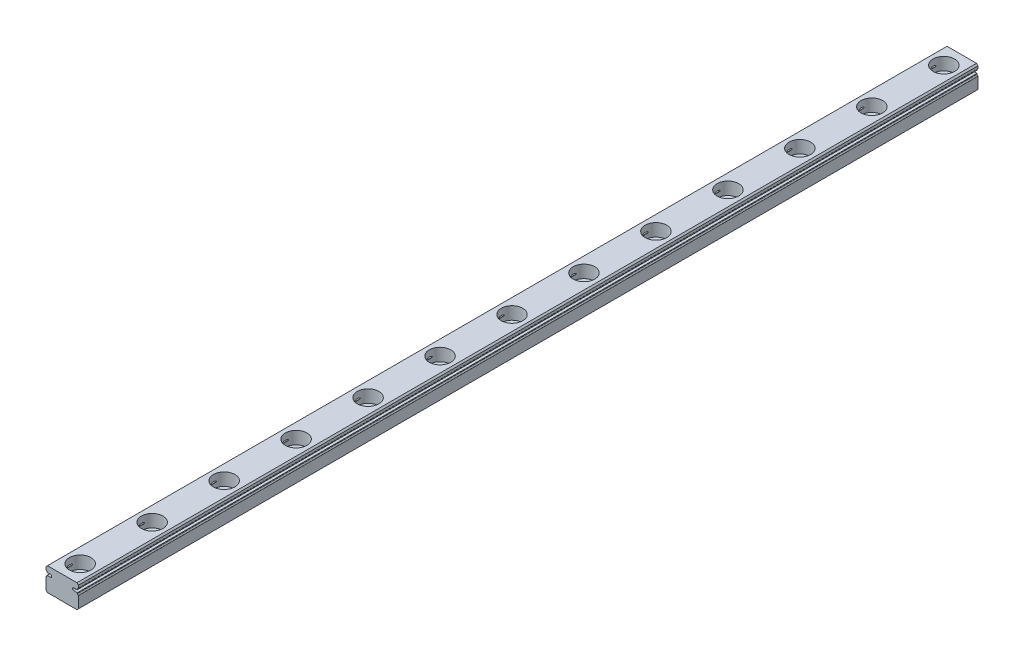
SolidWorks part; units mm, degrees
material "Acero al carbono no aleado"
ref_plane "Alzado" through (0, 0, 0) normal (0, 0, 1) x (1, 0, 0)
ref_plane "Planta" through (0, 0, 0) normal (0, 1, 0) x (1, 0, 0)
ref_plane "Vista lateral" through (0, 0, 0) normal (1, 0, 0) x (0, 0, -1)
ref_plane "Plano1" through (0, 3.3057, 0) normal (0, 1, 0) x (1, 0, 0)
sketch "Croquis1" plane through (0, 3.3057, 0) normal (0, 1, 0) x (1, 0, 0)
  line L0 (4.5, 250) -> (-4.5, 250)
  line L1 (-4.5, 250) -> (-4.5, -250)
  line L2 (-4.5, -250) -> (4.5, -250)
  line L3 (4.5, -250) -> (4.5, 250)
extrude "Saliente-Extruir1" add sketch "Croquis1" against normal blind 6.5
sketch "Croquis2" plane through (0, 0, -250) normal (0, 0, -1) x (-1, 0, 0)
  line L0 (1.6, -3.1943) -> (2.1, -3.1943)
  arc A0 (2.1, -3.1943) -> (1.6, -3.1943) centre (1.85, -3.4568) ccw
extrude "Cortar-Extruir1" cut sketch "Croquis2" against normal through all
sketch "Croquis3" plane through (0, 0, -250) normal (0, 0, -1) x (-1, 0, 0)
  line L0 (-4.5, 1.6457) -> (-4.5, 0.9457)
  line L1 (-4.5, 0.9457) -> (-3.25, 0.9457)
  line L2 (-3.25, 1.6457) -> (-4.5, 1.6457)
  arc A0 (-3.25, 0.9457) -> (-3.25, 1.6457) centre (-3.25, 1.2957) ccw
extrude "Cortar-Extruir2" cut sketch "Croquis3" against normal through all
sketch "Croquis4" plane through (0, 0, -250) normal (0, 0, -1) x (-1, 0, 0)
  line L0 (-4.3353, 0.9457) -> (-4.5, 0.9457)
  line L1 (-4.5, 0.9457) -> (-4.5, 0.4169)
  arc A0 (-4.5, 0.4169) -> (-4.3353, 0.9457) centre (-4.622, 0.745) ccw
extrude "Cortar-Extruir3" cut sketch "Croquis4" against normal through all
sketch "Croquis5" plane through (0, 0, -250) normal (0, 0, -1) x (-1, 0, 0)
  line L0 (-4.5, 2.1744) -> (-4.5, 1.6457)
  line L1 (-4.5, 1.6457) -> (-4.3353, 1.6457)
  arc A0 (-4.3353, 1.6457) -> (-4.5, 2.1744) centre (-4.622, 1.8464) ccw
extrude "Cortar-Extruir4" cut sketch "Croquis5" against normal through all
sketch "Croquis6" plane through (0, 0, -250) normal (0, 0, -1) x (-1, 0, 0)
  line L0 (4.5, 0.9457) -> (4.5, 1.6457)
  line L1 (4.5, 1.6457) -> (3.25, 1.6457)
  line L2 (3.25, 0.9457) -> (4.5, 0.9457)
  arc A0 (3.25, 1.6457) -> (3.25, 0.9457) centre (3.25, 1.2957) ccw
extrude "Cortar-Extruir5" cut sketch "Croquis6" against normal through all
sketch "Croquis7" plane through (0, 0, -250) normal (0, 0, -1) x (-1, 0, 0)
  line L0 (4.3353, 1.6457) -> (4.5, 1.6457)
  line L1 (4.5, 1.6457) -> (4.5, 2.1744)
  arc A0 (4.5, 2.1744) -> (4.3353, 1.6457) centre (4.622, 1.8464) ccw
extrude "Cortar-Extruir6" cut sketch "Croquis7" against normal through all
sketch "Croquis8" plane through (0, 0, -250) normal (0, 0, -1) x (-1, 0, 0)
  line L0 (4.5, 0.4169) -> (4.5, 0.9457)
  line L1 (4.5, 0.9457) -> (4.3353, 0.9457)
  arc A0 (4.3353, 0.9457) -> (4.5, 0.4169) centre (4.622, 0.745) ccw
extrude "Cortar-Extruir7" cut sketch "Croquis8" against normal through all
hole_wizard "Refrentado para tornillo con cabeza hexagonal de M31" positions "Croquis10" profile "Croquis9" counterbore size "M3" standard "Ansi Metric"
sketch "Croquis10" plane through (0, 3.3057, 0) normal (0, 1, 0) x (1, 0, 0)
  line L0 (-4.5, -250) -> (4.5, -250) construction
  point P0 (0, -245)
  point P1 (0, -225)
  point P2 (0, -205)
  point P3 (0, -185)
  point P4 (0, -165)
  point P5 (0, -145)
  point P6 (0, -125)
  point P7 (0, -105)
  point P8 (0, -85)
  point P9 (0, -65)
  point P10 (0, -45)
  point P11 (0, -25)
  point P21 (0, -5)
  dimension "D1" = 5
  dimension "D2" = 20
  dimension "D3" = 20
  dimension "D4" = 20
  dimension "D5" = 20
  dimension "D6" = 20
  dimension "D7" = 20
  dimension "D8" = 20
  dimension "D9" = 20
  dimension "D10" = 20
  dimension "D11" = 20
  dimension "D12" = 20
  dimension "D13" = 20
sketch "Croquis9" plane through (0, 3.3057, 245) normal (1, 0, 0) x (0, 0, 1)
  line L0 (0, 0) -> (0, 6.5)
  line L1 (0, 6.5) -> (1.75, 6.5)
  line L3 (1.75, 6.5) -> (1.75, 3.5)
  line L4 (1.75, 3.5) -> (3, 3.5)
  line L5 (3, 3.5) -> (3, 0)
  line L7 (3, 0) -> (0, 0)
  line L11 (0, -6.35) -> (0, 107.95) construction
  dimension "Diámetro de taladro hasta el siguiente" = 3.5
  dimension "Profundidad de taladro hasta el siguiente" = 6.5
  dimension "Diámetro de refrentado" = 6
  dimension "Profundidad de refrentado" = 3.5
chamfer "Chaflán1" distance 0.4 angle 45 4 edges at (-4.5, -3.1943, 0) (-4.5, 3.3057, 0) (4.5, -3.1943, 0) (4.5, 3.3057, 0)
chamfer "Chaflán2" distance 0.011 angle 36.529 4 edges at (-4.5, 2.1744, 0) (4.5, 0.4169, 0) (-4.5, 0.4169, 0) (4.5, 2.1744, 0) first distance on face at (-4.3528, 1.9303, 0) first distance on face at (4.3528, 0.6611, 0) first distance on face at (-4.5, -1.1887, 0) first distance on face at (4.5, 2.5401, 0)
chamfer "Chaflán3" distance 0.151 angle 53.471 4 edges at (-4.3353, 0.9457, 0) (4.3353, 0.9457, 0) (-4.3353, 1.6457, 0) (4.3353, 1.6457, 0) first distance on face at (-3.7926, 0.9457, 0) first distance on face at (4.3493, 0.6648, 0) first distance on face at (-4.3493, 1.9266, 0) first distance on face at (3.7926, 1.6457, 0)
sketch "Croquis11" plane through (0, 0, -250) normal (0, 0, -1) x (-1, 0, 0)
  line L1 (14.2088, 12.0295) -> (-12.4492, 12.0295)
  line L2 (14.2088, 12.0295) -> (14.2088, -16.4151)
  line L3 (14.2088, -16.4151) -> (-12.4492, -16.4151)
  line L4 (-12.4492, 12.0295) -> (-12.4492, -16.4151)
extrude "Cortar-Extruir8" cut sketch "Croquis11" against normal blind 250
